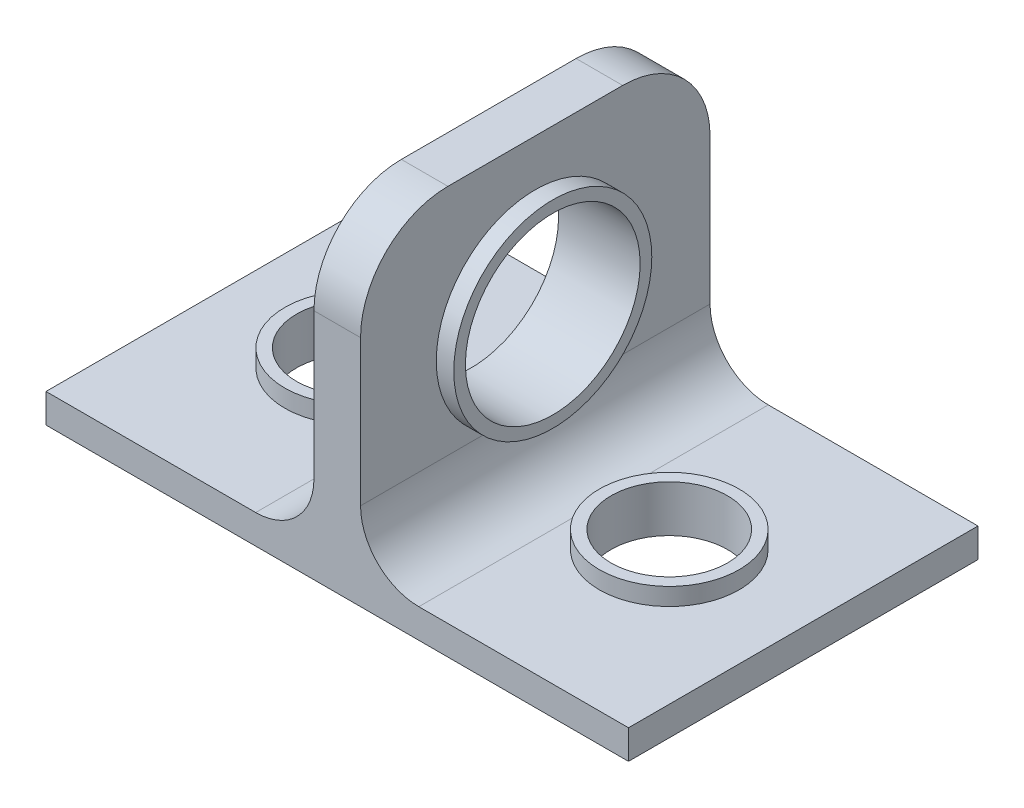
SolidWorks part; units mm, degrees
ref_plane "Front Plane" through (0, 0, 0) normal (0, 0, 1) x (1, 0, 0)
ref_plane "Top Plane" through (0, 0, 0) normal (0, 1, 0) x (1, 0, 0)
ref_plane "Right Plane" through (0, 0, 0) normal (1, 0, 0) x (0, 0, -1)
sketch "Sketch1" plane through (0, 0, 0) normal (0, 0, 1) x (1, 0, 0)
  line L0 (50, 0) -> (-50, 0)
  line L1 (-50, 0) -> (-50, 5)
  line L2 (-50, 5) -> (-14, 5)
  line L3 (-4, 15) -> (-4, 55)
  line L4 (-4, 55) -> (4, 55)
  line L5 (0, 0) -> (0, 55) construction
  line L6 (4, 15) -> (4, 55)
  line L7 (50, 5) -> (14, 5)
  line L8 (50, 0) -> (50, 5)
  arc A0 (4, 15) -> (14, 5) centre (14, 15) ccw
  arc A1 (-14, 5) -> (-4, 15) centre (-14, 15) ccw
  point P13 (4, 5)
  point P16 (-4, 5)
  dimension "D6" = 10
  dimension "D1" = 50
  dimension "D2" = 46
  dimension "D3" = 5
  dimension "D4" = 4
  dimension "D5" = 55
extrude "Boss-Extrude1" add sketch "Sketch1" along normal blind 30 and the other way blind 30
sketch "Sketch2" plane through (0, 5, 0) normal (0, 1, 0) x (1, 0, 0)
  line L0 (-14, -30) -> (-50, -30) construction
  line L1 (-50, 30) -> (-50, -30) construction
  circle A0 centre (-27, 0) radius 10
  circle A1 centre (-27, 0) radius 12
  dimension "D1" = 20
  dimension "D4" = 24
  dimension "D2" = 30
  dimension "D3" = 23
  dimension "D5" = 27
extrude "Cut-Extrude1" cut sketch "Sketch2" against normal up to surface (5 mm away) contours A0 up to face at (0, 0, 0)
extrude "Boss-Extrude2" add sketch "Sketch2<3>" along normal blind 3 contours A0 | A1
sketch "Sketch2<3>" plane through (0, 5, 0) normal (0, 1, 0) x (1, 0, 0) same geometry as "Sketch2"
mirror "Mirror1" about plane through (0, 0, 0) normal (1, 0, 0) of "Boss-Extrude2", "Cut-Extrude1"
sketch "Sketch3" plane through (-4, 0, 0) normal (-1, 0, 0) x (0, 0, 1)
  line L0 (-30, 0) -> (30, 0) construction
  line L2 (-30, 55) -> (30, 55) construction
  line L3 (30, 55) -> (30, 15) construction
  circle A0 centre (0, 30) radius 15
  circle A1 centre (0, 30) radius 17
  dimension "D1" = 30
  dimension "D5" = 34
  dimension "D2" = 30
  dimension "D3" = 55
  dimension "D4" = 30
extrude "Cut-Extrude2" cut sketch "Sketch3" against normal up to surface (8 mm away) contours A0 up to face at (4, 35, 0)
extrude "Boss-Extrude3" add sketch "Sketch3<3>" along normal blind 3 contours A0 | A1
sketch "Sketch3<3>" plane through (-4, 0, 0) normal (-1, 0, 0) x (0, 0, 1) same geometry as "Sketch3"
mirror "Mirror2" about plane through (0, 0, 0) normal (1, 0, 0) of "Boss-Extrude3"
fillet "Fillet1" radius 15 2 edges at (0, 55, 30) (0, 55, -30)
